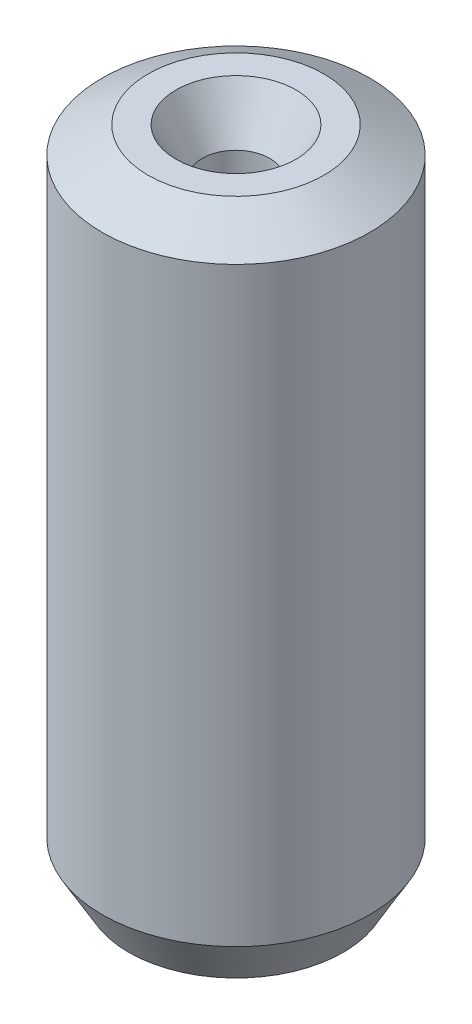
SolidWorks part; units mm, degrees
ref_plane "Front Plane" through (0, 0, 0) normal (0, 0, 1) x (1, 0, 0)
ref_plane "Top Plane" through (0, 0, 0) normal (0, 1, 0) x (1, 0, 0)
ref_plane "Right Plane" through (0, 0, 0) normal (1, 0, 0) x (0, 0, -1)
sketch "Sketch1" plane through (0, 0, 0) normal (0, 1, 0) x (1, 0, 0)
  circle A0 centre (0, 0) radius 5
  dimension "SLEEVE_OD" = 10
extrude "Boss-Extrude1" add sketch "Sketch1" along normal blind 24.7867
sketch "Sketch2" plane through (0, 0, 0) normal (0, 1, 0) x (1, 0, 0)
  circle A0 centre (0, 0) radius 1.2539
  dimension "BORE_D" = 2.5078
extrude "Cut-Extrude1" cut sketch "Sketch2" along normal through all
chamfer "Chamfer1" distance 0.9909 angle 60 4 edges at (0, 24.7867, 1.2539) (0, 0, 1.2539) (0, 0, 5) (0, 24.7867, 5) first distance on face at (0, 24.7867, 1.2539) first distance on face at (0, 0, 1.2539) first distance on face at (0, 24.7867, 5)
